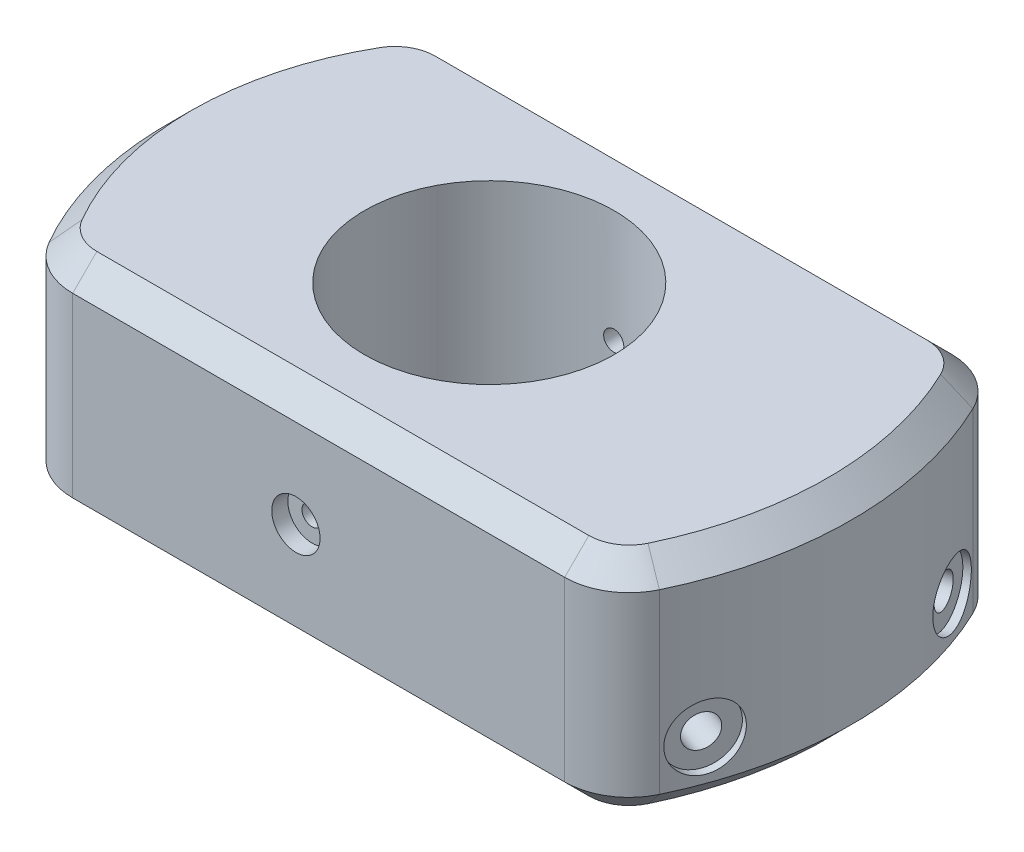
SolidWorks part; units mm, degrees
material "3D printed plastic"
ref_plane "Front Plane" through (0, 0, 0) normal (0, 0, 1) x (1, 0, 0)
ref_plane "Top Plane" through (0, 0, 0) normal (0, 1, 0) x (1, 0, 0)
ref_plane "Right Plane" through (0, 0, 0) normal (1, 0, 0) x (0, 0, -1)
sketch "Sketch1" plane through (0, 0, 0) normal (0, 1, 0) x (1, 0, 0)
  line L0 (-32, 24) -> (32, 24)
  line L1 (32, -24) -> (-32, -24)
  arc A0 (32, -24) -> (32, 24) centre (0, 0) ccw
  arc A1 (-32, 24) -> (-32, -24) centre (0, 0) ccw
  circle A2 centre (0, 0) radius 15.5
  dimension "D2" = 40
  dimension "D3" = 31
  dimension "D1" = 48
extrude "Boss-Extrude1" add sketch "Sketch1" along normal mid plane 28
sketch "Sketch3" plane through (0, 0, 0) normal (0, 0, 1) x (1, 0, 0)
  line L0 (-18, 2) -> (-52.4527, -4.0749) construction
  line L1 (-18, 2) -> (-19.4326, 10.1247)
  line L2 (-19.4326, 10.1247) -> (-53.8853, 4.0497)
  line L3 (-53.8853, 4.0497) -> (-52.4527, -4.0749)
  line L4 (-32, -14) -> (32, -14) construction
  line L5 (-18, 2) -> (-52.4527, -4.0749)
  dimension "D1" = 16.5
  dimension "D2" = 16
  dimension "D3" = 10
  dimension "D4" = 18
revolve "Cut-Revolve1" cut sketch "Sketch3" angle 360 about L0
ref_axis "Axis1" through (0, 14, 0) along (0, -1, 0)
ref_plane "Plane1" through (0, 0, 0) normal (-0.342, 0, 0.9397) x (0, -1, 0)
other "Move Face1" face at (36, 0, 0) offset 5 parameters "D1"=5
sketch "Sketch4" plane through (0, 0, 0) normal (-0.342, 0, 0.9397) x (0, -1, 0)
  line L0 (-6, 25) -> (33.5813, 35.6058) construction
  line L1 (-14, 0) -> (14, 0) construction
  line L2 (-6, 25) -> (-8.1353, 32.9689)
  line L3 (-8.1353, 32.9689) -> (31.446, 43.5747)
  line L4 (31.446, 43.5747) -> (33.5813, 35.6058)
  line L5 (14, -21.8617) -> (14, 43.9786) construction
  line L6 (-6, 25) -> (33.5813, 35.6058)
  dimension "D1" = 15
  dimension "D2" = 16.5
  dimension "D3" = 20
  dimension "D4" = 25
revolve "Cut-Revolve2" cut sketch "Sketch4" angle 360 about L0
sketch "Sketch6" plane through (0, 0, 0) normal (-0.342, 0, 0.9397) x (0, -1, 0)
  line L0 (4, 44) -> (4, 30) construction
  line L1 (14, 45) -> (-14, 45) construction
  line L2 (4, 30) -> (6, 30)
  line L3 (6, 30) -> (6, 45)
  line L4 (14, 45) -> (-14, 45) construction
  line L5 (14, -21.8617) -> (14, 43.9786) construction
  line L6 (4, 44) -> (4, 30)
  line L8 (2, 45) -> (2, 44)
  line L9 (2, 44) -> (4, 44)
  line L10 (2, 45) -> (2, 46)
  line L11 (2, 46) -> (6, 46)
  line L12 (6, 46) -> (6, 45)
  dimension "D1" = 10
  dimension "D2" = 4
  dimension "D3" = 15
  dimension "D4" = 4
  dimension "D5" = 1
  dimension "D6" = 1
revolve "Cut-Revolve3" cut sketch "Sketch6" angle 360 about L3
mirror "Mirror1" about plane through (0, 0, 0) normal (0, 0, 1) of "Cut-Revolve3", "Cut-Revolve2"
sketch "Sketch5" plane through (0, -14, 0) normal (0, -1, 0) x (1, 0, 0)
  line L0 (-30, 0) -> (0, 0) construction
  circle A0 centre (-30, 0) radius 2
  dimension "D2" = 4
  dimension "D1" = 30
extrude "Cut-Extrude2" cut sketch "Sketch5" against normal up to next
sketch "Sketch7" plane through (0, 0, 24) normal (0, 0, 1) x (1, 0, 0)
  circle A0 centre (0, 0) radius 1.25
  dimension "D1" = 2.5
extrude "Cut-Extrude3" cut sketch "Sketch7" against normal through all
fillet "Fillet1" radius 8 4 edges at (38.0657, 0, -24) (38.0657, 0, 24) (-32, 0, -24) (-32, 0, 24)
chamfer "Chamfer1" distance 3 angle 45 16 edges at (45, -14, 0) (37.6234, -14, -22.7704) (37.6234, -14, 22.7704) (2.8244, -14, -24) (2.8244, -14, 24) (-31.7128, -14, -22.9282) (-31.7128, -14, 22.9282) (-40, -14, 0) (45, 14, 0) (37.6234, 14, -22.7704) (37.6234, 14, 22.7704) (2.8244, 14, -24) (2.8244, 14, 24) (-31.7128, 14, -22.9282) (-31.7128, 14, 22.9282) (-40, 14, 0)
sketch "Sketch8" plane through (0, 0, 24) normal (0, 0, 1) x (1, 0, 0)
  circle A0 centre (0, 0) radius 3
  dimension "D1" = 6
extrude "Cut-Extrude4" cut sketch "Sketch8" against normal blind 2
mirror "Mirror2" about plane through (0, 0, 0) normal (0, 0, 1) of "Cut-Extrude4"
